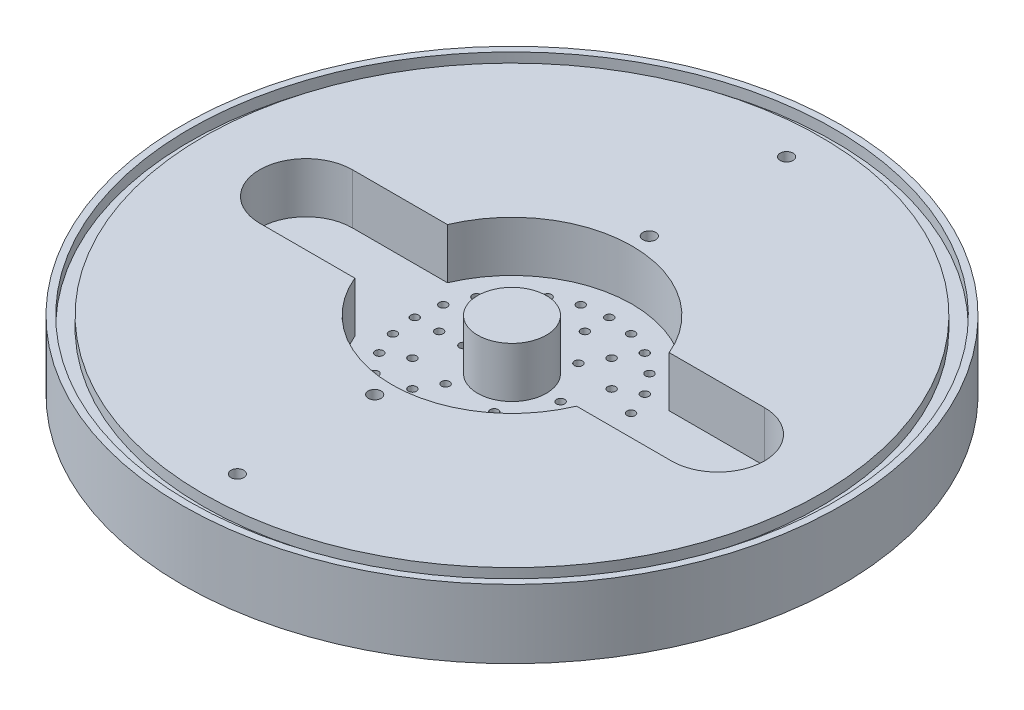
SolidWorks part; units mm, degrees
ref_plane "Front Plane" through (0, 0, 0) normal (0, 0, 1) x (1, 0, 0)
ref_plane "Top Plane" through (0, 0, 0) normal (0, 1, 0) x (1, 0, 0)
ref_plane "Right Plane" through (0, 0, 0) normal (1, 0, 0) x (0, 0, -1)
ref_axis "Axial" through (0, 0.508, 0) along (0, -1, 0)
ref_plane "Bottom Plane" through (0, -12.7, 0) normal (0, 1, 0) x (1, 0, 0)
sketch "Sketch1" plane through (0, 0, 0) normal (0, 1, 0) x (1, 0, 0)
  circle A0 centre (0, 0) radius 60.96
  dimension "D1" = 121.92
extrude "Billet" add sketch "Sketch1" against normal blind 12.7
sketch "Sketch4" plane through (0, -12.7, 0) normal (0, 1, 0) x (1, 0, 0)
  line L0 (0, 37.2675) -> (0, -28.2573) construction
  line L1 (-38.2015, 0) -> (37.6086, 0) construction
  circle A0 centre (8.9916, 0) radius 0.7493
  circle A1 centre (13.4874, 0) radius 0.7493
  circle A2 centre (17.9832, 0) radius 0.7493
  dimension "D1" = 1.4986
  dimension "D3" = 4.4958
  dimension "D4" = 4.4958
  dimension "D2" = 8.9916
extrude "First Kerosene Outlet" cut sketch "Sketch4" along normal through all and the other way through all
sketch "Sketch15" plane through (0, -12.7, 0) normal (0, 1, 0) x (1, 0, 0)
  circle A0 centre (0, 0) radius 57.15
  circle A1 centre (0, 0) radius 59.69
  dimension "D1" = 114.3
  dimension "D2" = 119.38
extrude "Chamber O Ring" cut sketch "Sketch15" along normal blind 2.032
sketch "Sketch16" plane through (0, 0, 0) normal (0, 1, 0) x (1, 0, 0)
  circle A0 centre (0, 0) radius 59.69
  circle A1 centre (0, 0) radius 57.15
  dimension "D1" = 119.38
  dimension "D2" = 114.3
extrude "Top O ring" cut sketch "Sketch16" against normal blind 2.032
pattern_circular "Primary Holes" count 6 over 360 about axis through (0, 0.508, 0) along (0, -1, 0) of "First Kerosene Outlet"
pattern_circular "Second ring" count 12 over 360 about axis through (0, 0.508, 0) along (0, -1, 0) skipping 2, 4, 6, 8, 10 of face at (13.4874, 0, 0.7493)
pattern_circular "Third Ring" count 24 over 360 about axis through (0, 0.508, 0) along (0, -1, 0) skipping 4, 8, 12, 16, 20 of face at (17.9832, 0, 0.7493)
sketch "Sketch18" plane through (0, 0, 0) normal (0, 1, 0) x (1, 0, 0)
  line L0 (-47.0718, 0) -> (54.8652, 0) construction
  line L1 (0, 40.3695) -> (0, -40.0578) construction
  line L2 (-38.1, 8.575) -> (-20.5041, 8.575)
  line L3 (-38.1, -8.575) -> (-20.5041, -8.575)
  line L4 (38.1, 8.575) -> (20.5041, 8.575)
  line L5 (38.1, -8.575) -> (20.5041, -8.575)
  arc A0 (-20.5041, -8.575) -> (20.5041, -8.575) centre (0, 0) ccw
  arc A1 (-38.1, 8.575) -> (-38.1, -8.575) centre (-38.1, 0) ccw
  arc A2 (38.1, 8.575) -> (38.1, -8.575) centre (38.1, 0) cw
  arc A3 (20.5041, 8.575) -> (-20.5041, 8.575) centre (0, 0) ccw
  dimension "D1" = 44.45
  dimension "D2" = 17.1501
  dimension "D3" = 38.1
extrude "Kerosene Well" cut sketch "Sketch18" against normal blind 9.3218
sketch "Sketch17" plane through (0, 0, 0) normal (0, 1, 0) x (1, 0, 0)
  circle A0 centre (0, 0) radius 6.35
  dimension "D1" = 12.7
extrude "Boss-Extrude1" add sketch "Sketch17" along normal blind 2.54 and the other way up to next
sketch "Sketch19" plane through (0, 2.54, 0) normal (0, 1, 0) x (1, 0, 0)
  circle A0 centre (0, 0) radius 6.35
  dimension "D1" = 12.7
extrude "Lox Tower" cut sketch "Sketch19" against normal blind 2.54
sketch "Sketch20" plane through (0, 0, 0) normal (0, 1, 0) x (1, 0, 0)
  line L0 (0, 68.1298) -> (0, -73.4056) construction
  line L1 (-6.985, 0) -> (6.985, 0) construction
  circle A0 centre (0, 25.4) radius 1.1906
  circle A1 centre (0, -25.4) radius 1.1906
  circle A2 centre (0, 50.8) radius 1.1906
  circle A3 centre (0, -50.8) radius 1.1906
  point P11 (0, 68.1298)
  point P12 (0, -73.4056)
  dimension "D1" = 2.3813
  dimension "D3" = 2.3813
  dimension "D2" = 25.4
  dimension "D4" = 50.8
extrude "Dowels" cut sketch "Sketch20" against normal blind 3.175
